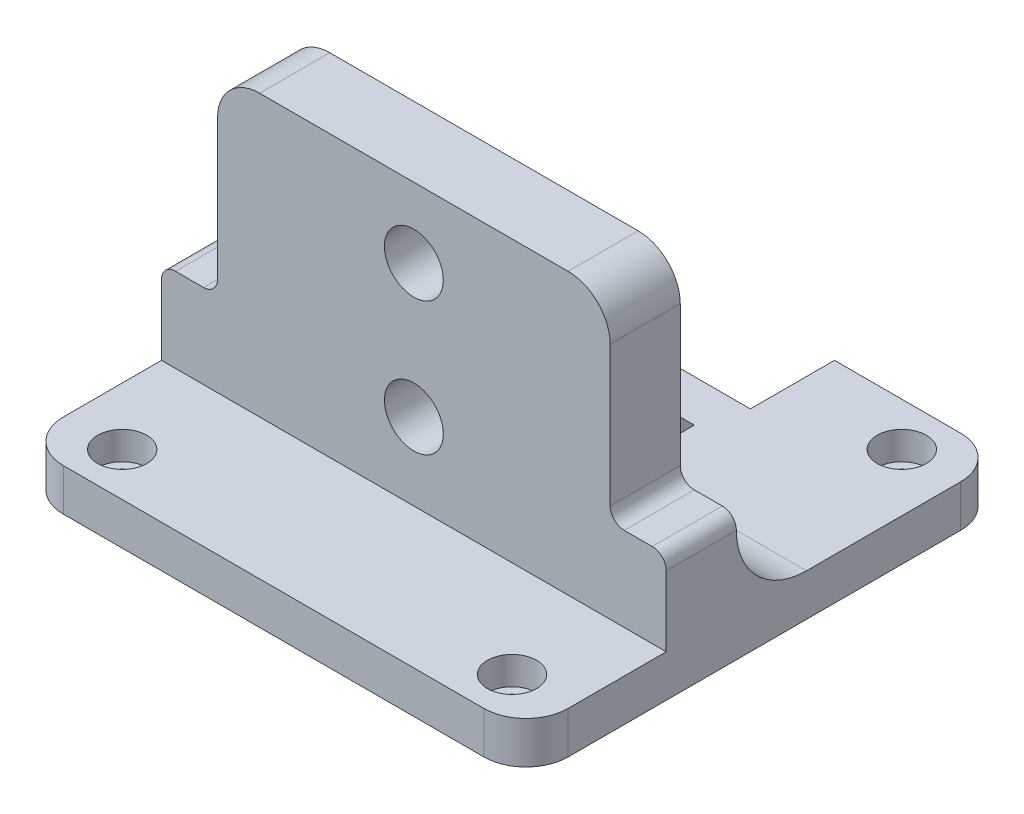
SolidWorks part; units mm, degrees
ref_plane "前视基准面" through (0, 0, 0) normal (0, 0, 1) x (1, 0, 0)
ref_plane "上视基准面" through (0, 0, 0) normal (0, 1, 0) x (1, 0, 0)
ref_plane "右视基准面" through (0, 0, 0) normal (1, 0, 0) x (0, 0, -1)
sketch "草图1" plane through (0, 0, 0) normal (0, 1, 0) x (1, 0, 0)
  line L0 (6, 17) -> (18, 17)
  line L1 (-18, 17) -> (-6, 17)
  line L2 (-18, 17) -> (-18, -17)
  line L3 (-18, -17) -> (18, -17)
  line L4 (18, 17) -> (18, -17)
  line L6 (6, 17) -> (6, 11)
  line L7 (6, 11) -> (-6, 11)
  line L8 (-6, 17) -> (-6, 11)
  point P4 (0, -17)
  point P6 (-18, 0)
  point P11 (0, 11)
  dimension "D1" = 36
  dimension "D2" = 34
  dimension "D3" = 12
  dimension "D4" = 11
extrude "凸台-拉伸1" add sketch "草图1" along normal blind 3
sketch "草图3" plane through (0, 3, 0) normal (0, 1, 0) x (1, 0, 0)
  line L0 (-18, -17) -> (18, -17) construction
  line L1 (18, -2) -> (-18, -2)
  line L2 (18, -2) -> (18, -7)
  line L3 (18, -7) -> (-18, -7)
  line L4 (-18, -2) -> (-18, -7)
  point P4 (0, -2)
  dimension "D1" = 36
  dimension "D2" = 5
  dimension "D3" = 10
extrude "凸台-拉伸3" add sketch "草图3" along normal blind 6 contours L3 L4 L1 L2
sketch "草图4" plane through (0, 9, 0) normal (0, 1, 0) x (1, 0, 0)
  line L0 (18, -2) -> (-18, -2) construction
  line L1 (-14, -2) -> (14, -2)
  line L2 (-14, -2) -> (-14, -7)
  line L3 (-14, -7) -> (14, -7)
  line L4 (14, -2) -> (14, -7)
  line L5 (18, -7) -> (-18, -7) construction
  point P8 (0, -2)
  dimension "D1" = 28
extrude "凸台-拉伸4" add sketch "草图4" along normal blind 14
sketch "草图6" plane through (0, 3, 0) normal (0, 1, 0) x (1, 0, 0)
  line L0 (14, -2) -> (-14, -2) construction
  line L1 (5, -2) -> (3, -2)
  line L2 (5, -2) -> (5, 8)
  line L3 (5, 8) -> (3, 8)
  line L4 (-5, -2) -> (-5, 8)
  line L5 (-3, 8) -> (-5, 8)
  line L7 (3, 8) -> (3, -2)
  line L9 (-3, 8) -> (-3, -2)
  line L10 (-3, -2) -> (-5, -2)
  dimension "D1" = 10
  dimension "D2" = 10
  dimension "D3" = 6
  dimension "D4" = 3
  dimension "D5" = 5
extrude "凸台-拉伸6" add sketch "草图6" along normal blind 10
chamfer "倒角1" distance 10 angle 45 2 edges at (4, 13, -8) (-4, 13, -8)
fillet "圆角2" radius 5 3 edges at (11.5, 3, 2) (-11.5, 3, 2) (0, 3, 2)
sketch "草图12" plane through (0, 0, 7) normal (0, 0, 1) x (1, 0, 0)
  line L0 (18, 3) -> (-18, 3) construction
  circle A0 centre (0, 18) radius 2.1
  circle A1 centre (0, 8.5) radius 2.1
  dimension "D1" = 4.2
  dimension "D2" = 15
  dimension "D3" = 9.5
extrude "切除-拉伸3" cut sketch "草图12" against normal through all
sketch "草图2" plane through (0, 0, 0) normal (0, -1, 0) x (1, 0, 0)
  line L2 (13.9, 13.9) -> (-13.9, 13.9) construction
  line L3 (-13.9, 13.9) -> (-13.9, -13.9) construction
  circle A4 centre (-13.9, 13.9) radius 1.1
  circle A5 centre (13.9, 13.9) radius 1.1
  circle A6 centre (-13.9, -13.9) radius 1.1
  circle A7 centre (13.9, -13.9) radius 1.1
  point P8 (0, 13.9)
  point P9 (-13.9, 0)
  dimension "D4" = 2.2
  dimension "D1" = 27.8
  dimension "D2" = 27.8
extrude "切除-拉伸4" cut sketch "草图2" against normal through all
sketch "草图13" plane through (0, 3, 0) normal (0, 1, 0) x (1, 0, 0)
  circle A0 centre (-13.9, 13.9) radius 1.75
  circle A1 centre (13.9, 13.9) radius 1.75
  circle A2 centre (-13.9, -13.9) radius 1.75
  circle A3 centre (13.9, -13.9) radius 1.75
  dimension "D1" = 3.5
extrude "切除-拉伸5" cut sketch "草图13" against normal blind 2
fillet "圆角3" radius 3 6 edges at (-18, 1.5, 17) (18, 1.5, 17) (-18, 1.5, -17) (18, 1.5, -17) (14, 23, 4.5) (-14, 23, 4.5)
fillet "圆角4" radius 1 4 edges at (18, 9, 4.5) (14, 9, 4.5) (-18, 9, 4.5) (-14, 9, 4.5)
